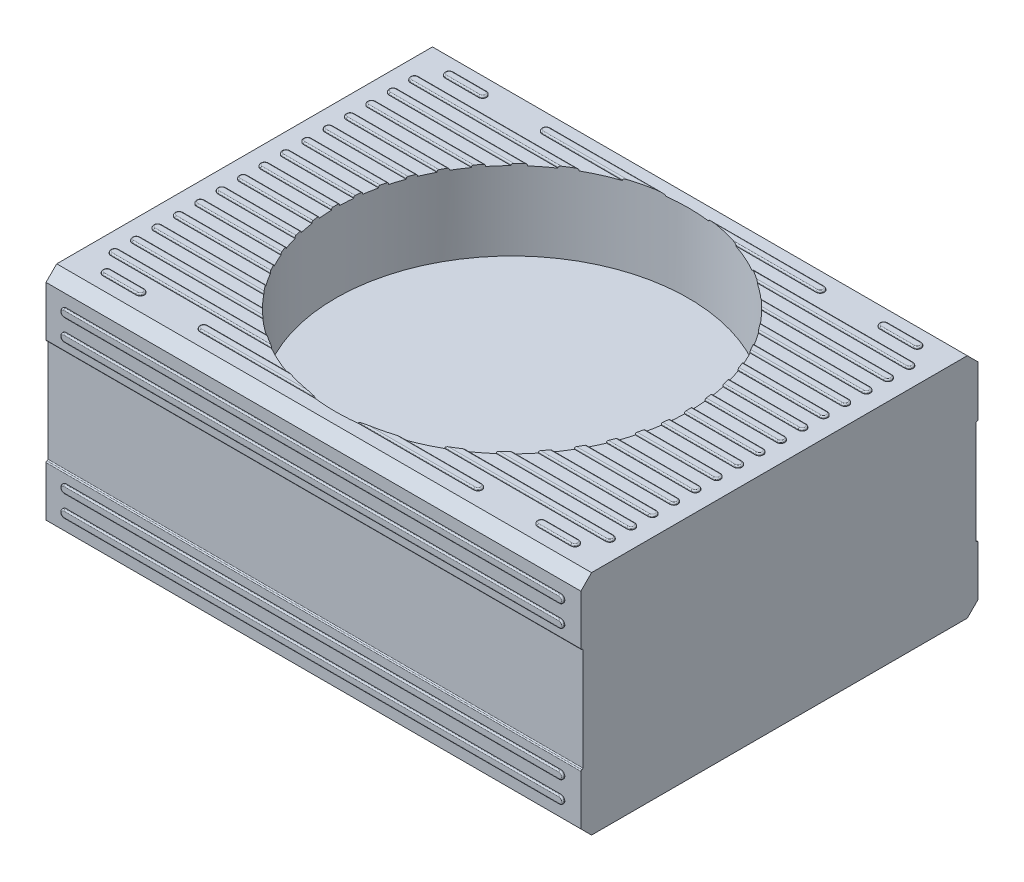
SolidWorks part; units mm, degrees
ref_plane "Front Plane" through (0, 0, 0) normal (0, 0, 1) x (1, 0, 0)
ref_plane "Top Plane" through (0, 0, 0) normal (0, 1, 0) x (1, 0, 0)
ref_plane "Right Plane" through (0, 0, 0) normal (1, 0, 0) x (0, 0, -1)
sketch "Sketch1" plane through (0, 0, 0) normal (0, 1, 0) x (1, 0, 0)
  line L1 (-100, -74.25) -> (100, -74.25)
  line L2 (-100, -74.25) -> (-100, 74.25)
  line L3 (-100, 74.25) -> (100, 74.25)
  line L4 (100, -74.25) -> (100, 74.25)
  line L5 (-100, -74.25) -> (100, 74.25) construction
  line L6 (-100, 74.25) -> (100, -74.25) construction
  point P0 (0, 0)
  dimension "D1" = 200
  dimension "D2" = 148.5
extrude "Boss-Extrude1" add sketch "Sketch1" along normal mid plane 85
chamfer "Chamfer1" distance 4 angle 45 4 edges at (0, -42.5, -74.25) (0, -42.5, 74.25) (0, 42.5, 74.25) (0, 42.5, -74.25)
sketch "Sketch3" plane through (0, 42.5, 0) normal (0, 1, 0) x (1, 0, 0)
  line L0 (-92.5, 0) -> (92.5, 0) construction
  line L1 (-92.5, 1.5) -> (92.5, 1.5)
  line L2 (-92.5, -1.5) -> (92.5, -1.5)
  line L3 (-92.5, 8) -> (92.5, 8) construction
  line L4 (-92.5, 9.5) -> (92.5, 9.5)
  line L5 (-92.5, 6.5) -> (92.5, 6.5)
  line L6 (-92.5, 16) -> (92.5, 16) construction
  line L7 (-92.5, 17.5) -> (92.5, 17.5)
  line L8 (-92.5, 14.5) -> (92.5, 14.5)
  line L9 (-92.5, 24) -> (92.5, 24) construction
  line L10 (-92.5, 25.5) -> (92.5, 25.5)
  line L11 (-92.5, 22.5) -> (92.5, 22.5)
  line L12 (-92.5, 32) -> (92.5, 32) construction
  line L13 (-92.5, 33.5) -> (92.5, 33.5)
  line L14 (-92.5, 30.5) -> (92.5, 30.5)
  line L15 (-92.5, 40) -> (92.5, 40) construction
  line L16 (-92.5, 41.5) -> (92.5, 41.5)
  line L17 (-92.5, 38.5) -> (92.5, 38.5)
  line L18 (-92.5, 48) -> (92.5, 48) construction
  line L19 (-92.5, 49.5) -> (92.5, 49.5)
  line L20 (-92.5, 46.5) -> (92.5, 46.5)
  line L21 (-92.5, 56) -> (92.5, 56) construction
  line L22 (-92.5, 57.5) -> (92.5, 57.5)
  line L23 (-92.5, 54.5) -> (92.5, 54.5)
  line L24 (-100, 0) -> (100, 0) construction
  line L25 (-100, 70.25) -> (-100, -70.25) construction
  line L26 (100, -70.25) -> (100, 70.25) construction
  line L27 (-87.5, 64) -> (-75, 64) construction
  line L28 (-87.5, 65.5) -> (-75, 65.5)
  line L29 (-87.5, 62.5) -> (-75, 62.5)
  line L30 (-51.25, 64) -> (51.25, 64) construction
  line L31 (-51.25, 65.5) -> (51.25, 65.5)
  line L32 (-51.25, 62.5) -> (51.25, 62.5)
  line L33 (75, 64) -> (87.5, 64) construction
  line L34 (75, 65.5) -> (87.5, 65.5)
  line L35 (75, 62.5) -> (87.5, 62.5)
  line L36 (-92.5, -8) -> (92.5, -8) construction
  line L37 (-92.5, -9.5) -> (92.5, -9.5)
  line L38 (-92.5, -6.5) -> (92.5, -6.5)
  line L39 (-92.5, -16) -> (92.5, -16) construction
  line L40 (-92.5, -17.5) -> (92.5, -17.5)
  line L41 (-92.5, -14.5) -> (92.5, -14.5)
  line L42 (-92.5, -24) -> (92.5, -24) construction
  line L43 (-92.5, -25.5) -> (92.5, -25.5)
  line L44 (-92.5, -22.5) -> (92.5, -22.5)
  line L45 (-92.5, -32) -> (92.5, -32) construction
  line L46 (-92.5, -33.5) -> (92.5, -33.5)
  line L47 (-92.5, -30.5) -> (92.5, -30.5)
  line L48 (-92.5, -40) -> (92.5, -40) construction
  line L49 (-92.5, -41.5) -> (92.5, -41.5)
  line L50 (-92.5, -38.5) -> (92.5, -38.5)
  line L51 (-92.5, -48) -> (92.5, -48) construction
  line L52 (-92.5, -49.5) -> (92.5, -49.5)
  line L53 (-92.5, -46.5) -> (92.5, -46.5)
  line L54 (-92.5, -56) -> (92.5, -56) construction
  line L55 (-92.5, -57.5) -> (92.5, -57.5)
  line L56 (-92.5, -54.5) -> (92.5, -54.5)
  line L57 (-87.5, -64) -> (-75, -64) construction
  line L58 (-87.5, -65.5) -> (-75, -65.5)
  line L59 (-87.5, -62.5) -> (-75, -62.5)
  line L60 (-51.25, -64) -> (51.25, -64) construction
  line L61 (-51.25, -65.5) -> (51.25, -65.5)
  line L62 (-51.25, -62.5) -> (51.25, -62.5)
  line L63 (75, -64) -> (87.5, -64) construction
  line L64 (75, -65.5) -> (87.5, -65.5)
  line L65 (75, -62.5) -> (87.5, -62.5)
  arc A0 (-92.5, 1.5) -> (-92.5, -1.5) centre (-92.5, 0) ccw
  arc A1 (92.5, -1.5) -> (92.5, 1.5) centre (92.5, 0) ccw
  arc A2 (-92.5, 9.5) -> (-92.5, 6.5) centre (-92.5, 8) ccw
  arc A3 (92.5, 6.5) -> (92.5, 9.5) centre (92.5, 8) ccw
  arc A4 (-92.5, 17.5) -> (-92.5, 14.5) centre (-92.5, 16) ccw
  arc A5 (92.5, 14.5) -> (92.5, 17.5) centre (92.5, 16) ccw
  arc A6 (-92.5, 25.5) -> (-92.5, 22.5) centre (-92.5, 24) ccw
  arc A7 (92.5, 22.5) -> (92.5, 25.5) centre (92.5, 24) ccw
  arc A8 (-92.5, 33.5) -> (-92.5, 30.5) centre (-92.5, 32) ccw
  arc A9 (92.5, 30.5) -> (92.5, 33.5) centre (92.5, 32) ccw
  arc A10 (-92.5, 41.5) -> (-92.5, 38.5) centre (-92.5, 40) ccw
  arc A11 (92.5, 38.5) -> (92.5, 41.5) centre (92.5, 40) ccw
  arc A12 (-92.5, 49.5) -> (-92.5, 46.5) centre (-92.5, 48) ccw
  arc A13 (92.5, 46.5) -> (92.5, 49.5) centre (92.5, 48) ccw
  arc A14 (-92.5, 57.5) -> (-92.5, 54.5) centre (-92.5, 56) ccw
  arc A15 (92.5, 54.5) -> (92.5, 57.5) centre (92.5, 56) ccw
  arc A16 (-87.5, 65.5) -> (-87.5, 62.5) centre (-87.5, 64) ccw
  arc A17 (-75, 62.5) -> (-75, 65.5) centre (-75, 64) ccw
  arc A18 (-51.25, 65.5) -> (-51.25, 62.5) centre (-51.25, 64) ccw
  arc A19 (51.25, 62.5) -> (51.25, 65.5) centre (51.25, 64) ccw
  arc A20 (75, 65.5) -> (75, 62.5) centre (75, 64) ccw
  arc A21 (87.5, 62.5) -> (87.5, 65.5) centre (87.5, 64) ccw
  arc A22 (-92.5, -9.5) -> (-92.5, -6.5) centre (-92.5, -8) cw
  arc A23 (92.5, -6.5) -> (92.5, -9.5) centre (92.5, -8) cw
  arc A24 (-92.5, -17.5) -> (-92.5, -14.5) centre (-92.5, -16) cw
  arc A25 (92.5, -14.5) -> (92.5, -17.5) centre (92.5, -16) cw
  arc A26 (-92.5, -25.5) -> (-92.5, -22.5) centre (-92.5, -24) cw
  arc A27 (92.5, -22.5) -> (92.5, -25.5) centre (92.5, -24) cw
  arc A28 (-92.5, -33.5) -> (-92.5, -30.5) centre (-92.5, -32) cw
  arc A29 (92.5, -30.5) -> (92.5, -33.5) centre (92.5, -32) cw
  arc A30 (-92.5, -41.5) -> (-92.5, -38.5) centre (-92.5, -40) cw
  arc A31 (92.5, -38.5) -> (92.5, -41.5) centre (92.5, -40) cw
  arc A32 (-92.5, -49.5) -> (-92.5, -46.5) centre (-92.5, -48) cw
  arc A33 (92.5, -46.5) -> (92.5, -49.5) centre (92.5, -48) cw
  arc A34 (-92.5, -57.5) -> (-92.5, -54.5) centre (-92.5, -56) cw
  arc A35 (92.5, -54.5) -> (92.5, -57.5) centre (92.5, -56) cw
  arc A36 (-87.5, -65.5) -> (-87.5, -62.5) centre (-87.5, -64) cw
  arc A37 (-75, -62.5) -> (-75, -65.5) centre (-75, -64) cw
  arc A38 (-51.25, -65.5) -> (-51.25, -62.5) centre (-51.25, -64) cw
  arc A39 (51.25, -62.5) -> (51.25, -65.5) centre (51.25, -64) cw
  arc A40 (75, -65.5) -> (75, -62.5) centre (75, -64) cw
  arc A41 (87.5, -62.5) -> (87.5, -65.5) centre (87.5, -64) cw
  point P2 (0, 0)
  point P12 (0, 8)
  point P19 (0, 16)
  point P26 (0, 24)
  point P33 (0, 32)
  point P40 (0, 40)
  point P47 (0, 48)
  point P54 (0, 56)
  point P65 (-81.25, 64)
  point P71 (0, 64)
  point P78 (81.25, 64)
  point P91 (0, -8)
  point P98 (0, -16)
  point P105 (0, -24)
  point P112 (0, -32)
  point P119 (0, -40)
  point P126 (0, -48)
  point P133 (0, -56)
  point P140 (-81.25, -64)
  point P147 (0, -64)
  point P154 (81.25, -64)
  dimension "D1" = 3
  dimension "D2" = 185
  dimension "D4" = 8
  dimension "D5" = 8
  dimension "D6" = 102.5
  dimension "D7" = 12.5
  dimension "D8" = 12.5
  dimension "D9" = 12.5
  dimension "D3" = 8
extrude "Boss-Extrude2" add sketch "Sketch3" along normal blind 0.75
fillet "Fillet1" radius 0.5 84 edges at (-81.25, 43.25, 62.5) (-73.5, 43.25, 64) (-81.25, 43.25, 65.5) (-89, 43.25, 64) (0, 43.25, 62.5) (52.75, 43.25, 64) (0, 43.25, 65.5) (-52.75, 43.25, 64) (81.25, 43.25, 62.5) (89, 43.25, 64) (81.25, 43.25, 65.5) (73.5, 43.25, 64) (0, 43.25, 54.5) (94, 43.25, 56) (0, 43.25, 57.5) (-94, 43.25, 56) (0, 43.25, 46.5) (94, 43.25, 48) (0, 43.25, 49.5) (-94, 43.25, 48) (0, 43.25, 38.5) (94, 43.25, 40) (0, 43.25, 41.5) (-94, 43.25, 40) (0, 43.25, 30.5) (94, 43.25, 32) (0, 43.25, 33.5) (-94, 43.25, 32) (0, 43.25, 22.5) (94, 43.25, 24) (0, 43.25, 25.5) (-94, 43.25, 24) (0, 43.25, 14.5) (94, 43.25, 16) (0, 43.25, 17.5) (-94, 43.25, 16) (0, 43.25, 6.5) (94, 43.25, 8) (0, 43.25, 9.5) (-94, 43.25, 8) (0, 43.25, -1.5) (94, 43.25, 0) (0, 43.25, 1.5) (-94, 43.25, 0) (0, 43.25, -9.5) (94, 43.25, -8) (0, 43.25, -6.5) (-94, 43.25, -8) (0, 43.25, -17.5) (94, 43.25, -16) (0, 43.25, -14.5) (-94, 43.25, -16) (0, 43.25, -25.5) (94, 43.25, -24) (0, 43.25, -22.5) (-94, 43.25, -24) (0, 43.25, -33.5) (94, 43.25, -32) (0, 43.25, -30.5) (-94, 43.25, -32) (0, 43.25, -41.5) (94, 43.25, -40) (0, 43.25, -38.5) (-94, 43.25, -40) (0, 43.25, -49.5) (94, 43.25, -48) (0, 43.25, -46.5) (-94, 43.25, -48) (0, 43.25, -57.5) (94, 43.25, -56) (0, 43.25, -54.5) (-94, 43.25, -56) (81.25, 43.25, -65.5) (89, 43.25, -64) (81.25, 43.25, -62.5) (73.5, 43.25, -64) (0, 43.25, -65.5) (52.75, 43.25, -64) (0, 43.25, -62.5) (-52.75, 43.25, -64) (-81.25, 43.25, -65.5) (-73.5, 43.25, -64) (-81.25, 43.25, -62.5) (-89, 43.25, -64)
sketch "Sketch2" plane through (0, 43.25, 0) normal (0, 1, 0) x (1, 0, 0)
  circle A0 centre (0, 0) radius 66
  dimension "D1" = 132
extrude "Cut-Extrude1" cut sketch "Sketch2" against normal blind 30
sketch "Sketch4" plane through (0, -42.5, 0) normal (0, -1, 0) x (1, 0, 0)
  line L0 (-92.5, 24.75) -> (92.5, 24.75) construction
  line L1 (-92.5, 26.25) -> (92.5, 26.25)
  line L2 (-92.5, 23.25) -> (92.5, 23.25)
  line L3 (-92.5, 32.75) -> (92.5, 32.75) construction
  line L4 (-92.5, 34.25) -> (92.5, 34.25)
  line L5 (-92.5, 31.25) -> (92.5, 31.25)
  line L6 (-92.5, 40.75) -> (92.5, 40.75) construction
  line L7 (-92.5, 42.25) -> (92.5, 42.25)
  line L8 (-92.5, 39.25) -> (92.5, 39.25)
  line L9 (-92.5, 48.75) -> (92.5, 48.75) construction
  line L10 (-92.5, 50.25) -> (92.5, 50.25)
  line L11 (-92.5, 47.25) -> (92.5, 47.25)
  line L12 (-92.5, 56.75) -> (92.5, 56.75) construction
  line L13 (-92.5, 58.25) -> (92.5, 58.25)
  line L14 (-92.5, 55.25) -> (92.5, 55.25)
  line L15 (-100, 74.25) -> (100, 74.25) construction
  line L16 (-100, 0) -> (100, 0) construction
  line L17 (-100, -70.25) -> (-100, 70.25) construction
  line L18 (100, 70.25) -> (100, -70.25) construction
  line L19 (-92.5, -24.75) -> (92.5, -24.75) construction
  line L20 (-92.5, -26.25) -> (92.5, -26.25)
  line L21 (-92.5, -23.25) -> (92.5, -23.25)
  line L22 (-92.5, -32.75) -> (92.5, -32.75) construction
  line L23 (-92.5, -34.25) -> (92.5, -34.25)
  line L24 (-92.5, -31.25) -> (92.5, -31.25)
  line L25 (-92.5, -40.75) -> (92.5, -40.75) construction
  line L26 (-92.5, -42.25) -> (92.5, -42.25)
  line L27 (-92.5, -39.25) -> (92.5, -39.25)
  line L28 (-92.5, -48.75) -> (92.5, -48.75) construction
  line L29 (-92.5, -50.25) -> (92.5, -50.25)
  line L30 (-92.5, -47.25) -> (92.5, -47.25)
  line L31 (-92.5, -56.75) -> (92.5, -56.75) construction
  line L32 (-92.5, -58.25) -> (92.5, -58.25)
  line L33 (-92.5, -55.25) -> (92.5, -55.25)
  arc A0 (-92.5, 26.25) -> (-92.5, 23.25) centre (-92.5, 24.75) ccw
  arc A1 (92.5, 23.25) -> (92.5, 26.25) centre (92.5, 24.75) ccw
  arc A2 (-92.5, 34.25) -> (-92.5, 31.25) centre (-92.5, 32.75) ccw
  arc A3 (92.5, 31.25) -> (92.5, 34.25) centre (92.5, 32.75) ccw
  arc A4 (-92.5, 42.25) -> (-92.5, 39.25) centre (-92.5, 40.75) ccw
  arc A5 (92.5, 39.25) -> (92.5, 42.25) centre (92.5, 40.75) ccw
  arc A6 (-92.5, 50.25) -> (-92.5, 47.25) centre (-92.5, 48.75) ccw
  arc A7 (92.5, 47.25) -> (92.5, 50.25) centre (92.5, 48.75) ccw
  arc A8 (-92.5, 58.25) -> (-92.5, 55.25) centre (-92.5, 56.75) ccw
  arc A9 (92.5, 55.25) -> (92.5, 58.25) centre (92.5, 56.75) ccw
  arc A10 (-92.5, -26.25) -> (-92.5, -23.25) centre (-92.5, -24.75) cw
  arc A11 (92.5, -23.25) -> (92.5, -26.25) centre (92.5, -24.75) cw
  arc A12 (-92.5, -34.25) -> (-92.5, -31.25) centre (-92.5, -32.75) cw
  arc A13 (92.5, -31.25) -> (92.5, -34.25) centre (92.5, -32.75) cw
  arc A14 (-92.5, -42.25) -> (-92.5, -39.25) centre (-92.5, -40.75) cw
  arc A15 (92.5, -39.25) -> (92.5, -42.25) centre (92.5, -40.75) cw
  arc A16 (-92.5, -50.25) -> (-92.5, -47.25) centre (-92.5, -48.75) cw
  arc A17 (92.5, -47.25) -> (92.5, -50.25) centre (92.5, -48.75) cw
  arc A18 (-92.5, -58.25) -> (-92.5, -55.25) centre (-92.5, -56.75) cw
  arc A19 (92.5, -55.25) -> (92.5, -58.25) centre (92.5, -56.75) cw
  point P2 (0, 24.75)
  point P11 (0, 32.75)
  point P18 (0, 40.75)
  point P25 (0, 48.75)
  point P32 (0, 56.75)
  point P46 (0, -24.75)
  point P53 (0, -32.75)
  point P60 (0, -40.75)
  point P67 (0, -48.75)
  point P74 (0, -56.75)
  dimension "D1" = 3
  dimension "D2" = 185
  dimension "D4" = 8
  dimension "D5" = 17.5
  dimension "D3" = 5
extrude "Boss-Extrude3" add sketch "Sketch4" along normal blind 0.75
sketch "Sketch5" plane through (0, 0, 74.25) normal (0, 0, 1) x (1, 0, 0)
  line L0 (-92.5, 32.5) -> (92.5, 32.5) construction
  line L1 (-92.5, 34) -> (92.5, 34)
  line L2 (-92.5, 31) -> (92.5, 31)
  line L3 (-100, 42.5) -> (100, 42.5) construction
  line L4 (-92.5, 24.5) -> (92.5, 24.5) construction
  line L5 (-92.5, 26) -> (92.5, 26)
  line L6 (-92.5, 23) -> (92.5, 23)
  line L7 (-100, 0) -> (100, 0) construction
  line L8 (-100, 38.5) -> (-100, -38.5) construction
  line L9 (100, 38.5) -> (100, -38.5) construction
  line L10 (-92.5, -32.5) -> (92.5, -32.5) construction
  line L11 (-92.5, -34) -> (92.5, -34)
  line L12 (-92.5, -31) -> (92.5, -31)
  line L13 (-92.5, -24.5) -> (92.5, -24.5) construction
  line L14 (-92.5, -26) -> (92.5, -26)
  line L15 (-92.5, -23) -> (92.5, -23)
  arc A0 (-92.5, 34) -> (-92.5, 31) centre (-92.5, 32.5) ccw
  arc A1 (92.5, 31) -> (92.5, 34) centre (92.5, 32.5) ccw
  arc A2 (-92.5, 26) -> (-92.5, 23) centre (-92.5, 24.5) ccw
  arc A3 (92.5, 23) -> (92.5, 26) centre (92.5, 24.5) ccw
  arc A4 (-92.5, -34) -> (-92.5, -31) centre (-92.5, -32.5) cw
  arc A5 (92.5, -31) -> (92.5, -34) centre (92.5, -32.5) cw
  arc A6 (-92.5, -26) -> (-92.5, -23) centre (-92.5, -24.5) cw
  arc A7 (92.5, -23) -> (92.5, -26) centre (92.5, -24.5) cw
  point P2 (0, 32.5)
  point P13 (0, 24.5)
  point P25 (0, -32.5)
  point P32 (0, -24.5)
  dimension "D1" = 185
  dimension "D2" = 10
  dimension "D3" = 3
  dimension "D5" = 8
  dimension "D4" = 2
extrude "Boss-Extrude4" add sketch "Sketch5" along normal blind 0.75
sketch "Sketch6" plane through (0, 0, 74.25) normal (0, 0, 1) x (1, 0, 0)
  line L0 (100, 38.5) -> (100, -38.5) construction
  line L1 (-100, -19.5) -> (100, -19.5)
  line L2 (-100, -19.5) -> (-100, 19.5)
  line L3 (-100, 19.5) -> (100, 19.5)
  line L4 (100, -19.5) -> (100, 19.5)
  line L5 (-100, -19.5) -> (100, 19.5) construction
  line L6 (-100, 19.5) -> (100, -19.5) construction
  arc A0 (92.5, 23) -> (92.5, 26) centre (92.5, 24.5) ccw construction
  point P0 (0, 0)
  dimension "D1" = 5
extrude "Cut-Extrude2" cut sketch "Sketch6" against normal blind 0.75
mirror "Mirror1" about plane through (0, 0, 0) normal (0, 0, 1) of "Boss-Extrude4", "Cut-Extrude2"
fillet "Fillet2" radius 0.5 72 edges at (0, -43.25, 58.25) (94, -43.25, 56.75) (0, -43.25, 55.25) (-94, -43.25, 56.75) (0, -43.25, 50.25) (94, -43.25, 48.75) (0, -43.25, 47.25) (-94, -43.25, 48.75) (0, -43.25, 42.25) (94, -43.25, 40.75) (0, -43.25, 39.25) (-94, -43.25, 40.75) (0, -43.25, 34.25) (94, -43.25, 32.75) (0, -43.25, 31.25) (-94, -43.25, 32.75) (0, -43.25, 26.25) (94, -43.25, 24.75) (0, -43.25, 23.25) (-94, -43.25, 24.75) (0, -43.25, -23.25) (94, -43.25, -24.75) (0, -43.25, -26.25) (-94, -43.25, -24.75) (0, -43.25, -31.25) (94, -43.25, -32.75) (0, -43.25, -34.25) (-94, -43.25, -32.75) (0, -43.25, -39.25) (94, -43.25, -40.75) (0, -43.25, -42.25) (-94, -43.25, -40.75) (0, -43.25, -47.25) (94, -43.25, -48.75) (0, -43.25, -50.25) (-94, -43.25, -48.75) (0, -43.25, -55.25) (94, -43.25, -56.75) (0, -43.25, -58.25) (-94, -43.25, -56.75) (0, -34, -75) (94, -32.5, -75) (0, -31, -75) (-94, -32.5, -75) (0, -26, -75) (94, -24.5, -75) (0, -23, -75) (-94, -24.5, -75) (0, 23, -75) (94, 24.5, -75) (0, 26, -75) (-94, 24.5, -75) (0, 31, -75) (94, 32.5, -75) (0, 34, -75) (-94, 32.5, -75) (0, -31, 75) (94, -32.5, 75) (0, -34, 75) (-94, -32.5, 75) (0, -23, 75) (94, -24.5, 75) (0, -26, 75) (-94, -24.5, 75) (0, 26, 75) (94, 24.5, 75) (0, 23, 75) (-94, 24.5, 75) (0, 34, 75) (94, 32.5, 75) (0, 31, 75) (-94, 32.5, 75)
fillet "Fillet3" radius 0.375 8 edges at (0, 19.5, 73.5) (0, 19.5, 74.25) (0, -19.5, 73.5) (0, -19.5, 74.25) (0, -19.5, -73.5) (0, -19.5, -74.25) (0, 19.5, -74.25) (0, 19.5, -73.5)
sketch "Sketch8" plane through (-100, 0, 0) normal (-1, 0, 0) x (0, 0, 1)
  line L0 (73.5, 19.125) -> (73.5, -19.125) construction
  line L5 (41, 14.5) -> (56, 14.5)
  line L6 (38, 11.5) -> (38, -11.5)
  line L7 (41, -14.5) -> (56, -14.5)
  line L8 (59, 11.5) -> (59, -11.5)
  line L9 (43.25, 9.5) -> (44.75, 9.5)
  line L10 (43.25, 9.5) -> (43.25, 5.5)
  line L11 (43.25, 5.5) -> (44.75, 5.5)
  line L12 (44.75, 9.5) -> (44.75, 5.5)
  line L13 (43.25, -5.5) -> (44.75, -5.5)
  line L14 (43.25, -5.5) -> (43.25, -9.5)
  line L15 (43.25, -9.5) -> (44.75, -9.5)
  line L16 (44.75, -5.5) -> (44.75, -9.5)
  line L17 (52.25, 2.5) -> (53.75, 2.5)
  line L18 (52.25, 2.5) -> (52.25, -2.5)
  line L19 (52.25, -2.5) -> (53.75, -2.5)
  line L20 (53.75, 2.5) -> (53.75, -2.5)
  arc A0 (41, 14.5) -> (38, 11.5) centre (41, 11.5) ccw
  arc A1 (38, -11.5) -> (41, -14.5) centre (41, -11.5) ccw
  arc A2 (56, -14.5) -> (59, -11.5) centre (56, -11.5) ccw
  arc A3 (56, 14.5) -> (59, 11.5) centre (56, 11.5) cw
  point P4 (38, 0)
  point P18 (52.25, 0)
  point P19 (43.25, 7.5)
  point P20 (43.25, -7.5)
  point P21 (44, 9.5)
  point P22 (53, 2.5)
  point P23 (48.5, 14.5)
  point P28 (38, 14.5)
  point P33 (59, -14.5)
  point P36 (59, 14.5)
  dimension "D11" = 3
  dimension "D1" = 21
  dimension "D2" = 29
  dimension "D3" = 1.5
  dimension "D4" = 4
  dimension "D5" = 7.5
  dimension "D6" = 7.5
  dimension "D7" = 6
  dimension "D8" = 6
  dimension "D9" = 5
  dimension "D10" = 25
extrude "Cut-Extrude3" cut sketch "Sketch8" against normal blind 17.5
sketch "Sketch9" plane through (-100, 0, 0) normal (-1, 0, 0) x (0, 0, 1)
  line L0 (41, -14.5) -> (56, -14.5) construction
  line L1 (59, -11.5) -> (59, 11.5) construction
  line L2 (56, 14.5) -> (41, 14.5) construction
  line L3 (38, 11.5) -> (38, -11.5) construction
  line L4 (41, -14.5) -> (56, -14.5)
  line L5 (59, -11.5) -> (59, 11.5)
  line L6 (56, 14.5) -> (41, 14.5)
  line L7 (38, 11.5) -> (38, -11.5)
  line L9 (36, 18) -> (61, 18)
  line L10 (34.5, 16.5) -> (34.5, -16.5)
  line L11 (36, -18) -> (61, -18)
  line L12 (62.5, 16.5) -> (62.5, -16.5)
  arc A0 (38, -11.5) -> (41, -14.5) centre (41, -11.5) ccw construction
  arc A1 (56, -14.5) -> (59, -11.5) centre (56, -11.5) ccw construction
  arc A2 (59, 11.5) -> (56, 14.5) centre (56, 11.5) ccw construction
  arc A3 (41, 14.5) -> (38, 11.5) centre (41, 11.5) ccw construction
  arc A4 (38, -11.5) -> (41, -14.5) centre (41, -11.5) ccw
  arc A5 (56, -14.5) -> (59, -11.5) centre (56, -11.5) ccw
  arc A6 (59, 11.5) -> (56, 14.5) centre (56, 11.5) ccw
  arc A7 (41, 14.5) -> (38, 11.5) centre (41, 11.5) ccw
  arc A8 (61, -18) -> (62.5, -16.5) centre (61, -16.5) ccw
  arc A9 (34.5, -16.5) -> (36, -18) centre (36, -16.5) ccw
  arc A10 (36, 18) -> (34.5, 16.5) centre (36, 16.5) ccw
  arc A11 (61, 18) -> (62.5, 16.5) centre (61, 16.5) cw
  point P13 (34.5, 0)
  point P16 (38, 0)
  point P18 (48.5, 18)
  point P19 (48.5, 14.5)
  point P22 (62.5, -18)
  point P27 (34.5, 18)
  point P30 (62.5, 18)
  dimension "D3" = 1.5
  dimension "D1" = 28
  dimension "D2" = 36
extrude "Boss-Extrude5" add sketch "Sketch9" along normal blind 2.5
sketch "Sketch10" plane through (-100, 0, 0) normal (-1, 0, 0) x (0, 0, 1)
  line L0 (73.5, 19.125) -> (73.5, -19.125) construction
  line L1 (13.5, 10) -> (28.5, 10)
  line L2 (13.5, 10) -> (13.5, -10)
  line L3 (13.5, -10) -> (28.5, -10)
  line L4 (28.5, 10) -> (28.5, -10)
  point P4 (13.5, 0)
  point P6 (21, 10)
  dimension "D1" = 15
  dimension "D2" = 20
  dimension "D3" = 52.5
extrude "Boss-Extrude6" add sketch "Sketch10" along normal blind 2
sketch "Sketch11" plane through (-102, 0, 0) normal (-1, 0, 0) x (0, 0, 1)
  line L0 (13.5, 10) -> (13.5, -10) construction
  line L1 (28.5, 10) -> (13.5, 10) construction
  line L2 (13.5, -10) -> (28.5, -10) construction
  arc A0 (16.9293, 6.8533) -> (16.9293, -6.8533) centre (40.9716, 0) ccw
  arc A1 (25.0707, 6.8533) -> (25.0707, -6.8533) centre (1.0284, 0) cw
  arc A2 (16.9293, 6.8533) -> (25.0707, 6.8533) centre (21, -2.2807) cw
  arc A3 (16.9293, -6.8533) -> (25.0707, -6.8533) centre (21, 2.2807) ccw
  point P8 (15.9716, 0)
  point P11 (13.5, 0)
  point P12 (26.0284, 0)
  point P13 (21, 7.7193)
  point P16 (21, 10)
  point P19 (21, -10)
  dimension "D1" = 25
  dimension "D2" = 10
extrude "Cut-Extrude4" cut sketch "Sketch11" against normal blind 10
